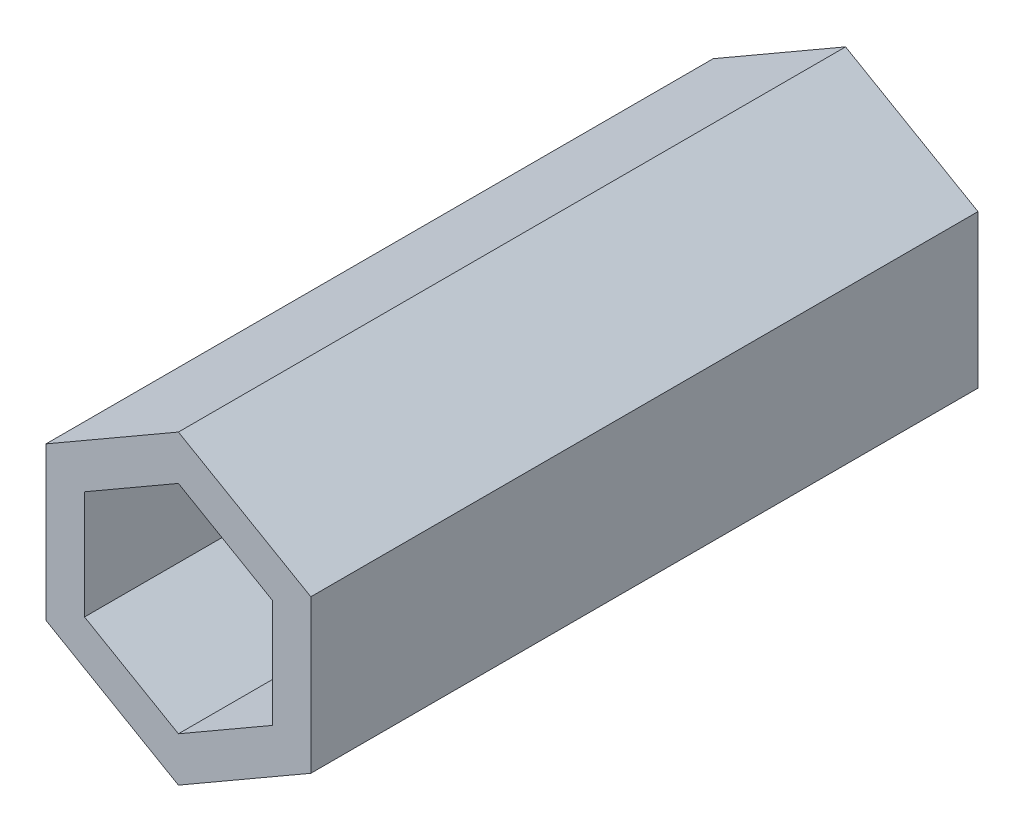
SolidWorks part; units mm, degrees
ref_plane "Front Plane" through (0, 0, 0) normal (0, 0, 1) x (1, 0, 0)
ref_plane "Top Plane" through (0, 0, 0) normal (0, 1, 0) x (1, 0, 0)
ref_plane "Right Plane" through (0, 0, 0) normal (1, 0, 0) x (0, 0, -1)
sketch "Sketch1" plane through (0, 0, 0) normal (0, 0, 1) x (1, 0, 0)
  line L1 (0, -11) -> (9.5263, -5.5)
  line L2 (9.5263, -5.5) -> (9.5263, 5.5)
  line L3 (9.5263, 5.5) -> (0, 11)
  line L4 (0, 11) -> (-9.5263, 5.5)
  line L5 (-9.5263, 5.5) -> (-9.5263, -5.5)
  line L6 (-9.5263, -5.5) -> (0, -11)
  circle A0 centre (0, 0) radius 11
  circle A1 centre (0, 0) radius 9.5263 construction
  circle A2 centre (0, 0) radius 6.4
  dimension "D1" = 22
  dimension "D2" = 12.8
extrude "Boss-Extrude1" [suppressed] add sketch "Sketch1" along normal mid plane 20 contours L4 A0 | L5 A0 | L5 L6 L1 L2 L3 L4 | L3 A0 | L2 A0 | L1 A0 | L6 A0
extrude "Boss-Extrude2" add sketch "Sketch1<3>" along normal mid plane 48 separate body contours L5 L6 L1 L2 L3 L4 A2 | A2 region at (-4.6176, -7.998, 0)
sketch "Sketch1<3>" plane through (0, 0, 0) normal (0, 0, 1) x (1, 0, 0) same geometry as "Sketch1"
sketch "Sketch2" plane through (0, 0, 0) normal (0, 0, 1) x (1, 0, 0)
  line L1 (0, -7.8) -> (6.755, -3.9)
  line L2 (6.755, -3.9) -> (6.755, 3.9)
  line L3 (6.755, 3.9) -> (0, 7.8)
  line L4 (0, 7.8) -> (-6.755, 3.9)
  line L5 (-6.755, 3.9) -> (-6.755, -3.9)
  line L6 (-6.755, -3.9) -> (0, -7.8)
  circle A0 centre (0, 0) radius 6.755 construction
  dimension "D1" = 15.6
extrude "Cut-Extrude3" cut sketch "Sketch2" against normal through all both and the other way through all
